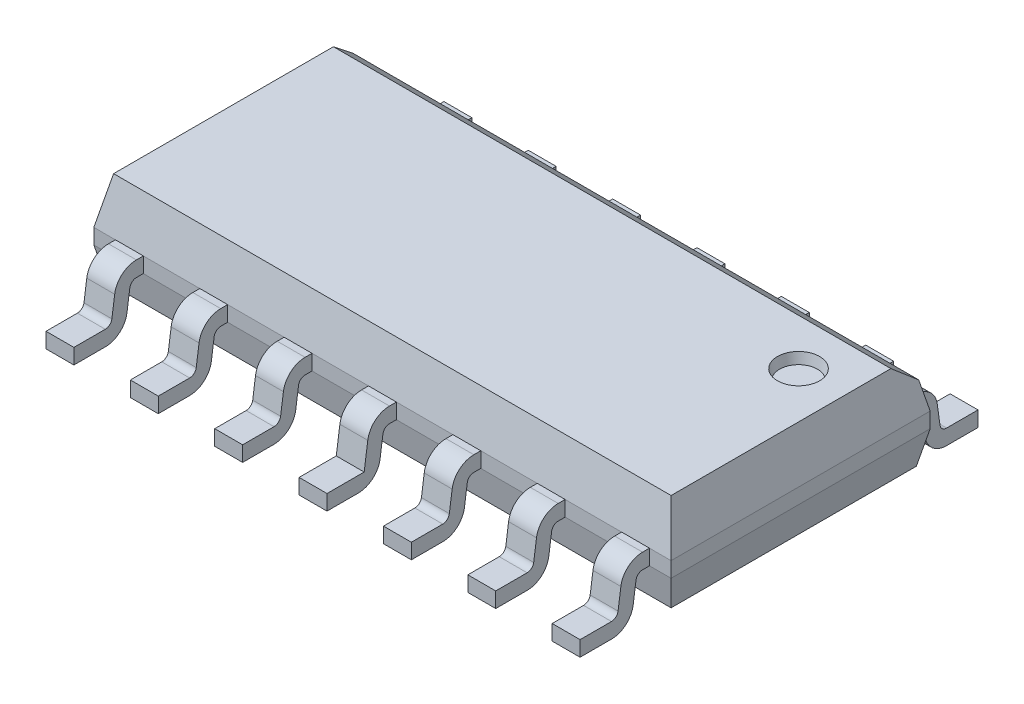
SolidWorks part; units mm, degrees
note: '?' marks a value the reader was unsure of.
ref_plane "Front Plane" through (0, 0, 0) normal (0, 0, 1) x (1, 0, 0)
ref_plane "Top Plane" through (0, 0, 0) normal (0, 1, 0) x (1, 0, 0)
ref_plane "Right Plane" through (0, 0, 0) normal (1, 0, 0) x (0, 0, -1)
ref_axis "Axis1" through (4.7795, 0, 0) along (-1, 0, 0)?
sketch "Sketch1" plane through (0, 0, 0) normal (0, 1, 0) x (1, 0, 0)
  line L1 (-4.345, 1.95) -> (4.345, 1.95)
  line L2 (-4.345, 1.95) -> (-4.345, -1.95)
  line L3 (-4.345, -1.95) -> (4.345, -1.95)
  line L4 (4.345, 1.95) -> (4.345, -1.95)
  dimension "D1" = 8.69
  dimension "D2" = 3.9
  dimension "D3" = 4.345
  dimension "D4" = 1.95
extrude "Extrude1" add sketch "Sketch1" along normal blind 0.7 draft 12 and the other way blind 0.23
sketch "Sketch2" plane through (0, -0.23, 0) normal (0, -1, 0) x (1, 0, 0)
  line L4 (-4.345, 1.95) -> (-4.345, -1.95)
  line L5 (-4.345, -1.95) -> (4.345, -1.95)
  line L6 (4.345, -1.95) -> (4.345, 1.95)
  line L7 (4.345, 1.95) -> (-4.345, 1.95)
  line L8 (-4.345, 1.95) -> (-4.345, -1.95)
  line L9 (-4.345, -1.95) -> (4.345, -1.95)
  line L10 (4.345, -1.95) -> (4.345, 1.95)
  line L11 (4.345, 1.95) -> (-4.345, 1.95)
  dimension "D1" = 0
extrude "Extrude2" add sketch "Sketch2" along normal blind 0.49 draft 12
chamfer "Chamfer1" distance 0.3 angle 38.5 1 edges at (0, 0.7, -1.8012)
sketch "Sketch3" plane through (0, 0.7, 0) normal (0, 1, 0) x (-1, 0, 0)
  circle A0 centre (-3.5015, -0.8119) radius 0.3175
extrude "Cut-Extrude1" cut sketch "Sketch3" against normal blind 0.15 draft 12
sketch "Sketch4" plane through (0, 0, 0) normal (1, 0, 0) x (0, 0, -1)
  line L0 (1.95, -0.23) -> (-1.95, -0.23) construction
  line L1 (1.95, 0) -> (-1.95, 0) construction
  line L2 (1.95, -0.23) -> (-1.95, -0.23)
  line L3 (1.95, 0) -> (-1.95, 0)
  line L4 (-1.8458, -0.72) -> (1.8458, -0.72) construction
  line L5 (2.995, -0.67) -> (2.4354, -0.67)
  line L6 (2.995, -0.67) -> (2.995, -0.9)
  line L7 (2.995, -0.9) -> (2.2355, -0.9)
  line L8 (2.155, -0.67) -> (2.155, -0.9) construction
  line L9 (-2.155, -0.67) -> (-2.4354, -0.67) construction
  line L10 (-2.155, -0.67) -> (-2.155, -0.9) construction
  line L11 (-2.155, -0.9) -> (-2.2355, -0.9) construction
  line L12 (-2.995, -0.67) -> (-2.995, -0.9)
  line L13 (1.95, 0) -> (2.3413, 0)
  line L14 (2.6703, 0) -> (2.6703, -0.23) construction
  line L15 (2.6703, -0.23) -> (2.1413, -0.23) construction
  line L16 (-1.95, 0) -> (-2.3413, 0)
  line L17 (-2.6934, 0) -> (-2.6934, -0.23) construction
  line L18 (-2.6934, -0.23) -> (-2.1413, -0.23) construction
  line L19 (2.3413, 0) -> (2.6703, 0) construction
  line L20 (2.4354, -0.67) -> (2.3413, 0)
  line L21 (2.2355, -0.9) -> (2.1413, -0.23)
  line L22 (2.1413, -0.23) -> (1.95, -0.23)
  line L23 (2.2355, -0.9) -> (2.155, -0.9) construction
  line L24 (2.4354, -0.67) -> (2.155, -0.67) construction
  line L25 (0, -1.1578) -> (0, -1.9582) construction
  line L26 (-2.2355, -0.9) -> (-2.1413, -0.23)
  line L27 (-2.4354, -0.67) -> (-2.3413, 0)
  line L28 (-2.1413, -0.23) -> (-1.95, -0.23)
  line L29 (-2.3413, 0) -> (-2.6934, 0) construction
  line L30 (-2.4354, -0.67) -> (-2.995, -0.67)
  line L31 (-2.2355, -0.9) -> (-2.995, -0.9)
  dimension "D1" = 0.84
  dimension "D2" = 5.99
  dimension "D3" = 2.995
  dimension "D4" = 0.18
  dimension "D5" = 0.23
  dimension "D6" = 0.23
extrude "Extrude3" add sketch "Sketch4" along normal blind 0.21 and the other way blind 0.21
pattern_linear "LPattern3" count 4 spacing 1.27 along (1, 0, 0) count 4 spacing 1.27 along (-1, 0, 0) of "Extrude3"
fillet "Fillet1" radius 0.1 27 edges at (-1.27, -0.23, 2.1413) (-1.27, -0.23, -2.1413) (-1.27, -0.67, -2.4354) (-1.27, -0.67, 2.4354) (-2.54, -0.23, 2.1413) (-2.54, -0.23, -2.1413) (-2.54, -0.67, -2.4354) (-2.54, -0.67, 2.4354) (-3.81, -0.23, 2.1413) (-3.81, -0.23, -2.1413) (-3.81, -0.67, -2.4354) (-3.81, -0.67, 2.4354) (1.27, -0.23, 2.1413) (1.27, -0.23, -2.1413) (1.27, -0.67, -2.4354) (1.27, -0.67, 2.4354) (2.54, -0.23, 2.1413) (2.54, -0.23, -2.1413) (2.54, -0.67, -2.4354) (2.54, -0.67, 2.4354) (3.81, -0.23, 2.1413) (3.81, -0.23, -2.1413) (3.81, -0.67, -2.4354) (3.81, -0.67, 2.4354) (0, -0.23, 2.1413) (0, -0.23, -2.1413) (0, -0.67, -2.4354)
fillet "Fillet2" radius 0.33 28 edges at (-1.27, 0, -2.3413) (-1.27, -0.9, -2.2355) (-1.27, 0, 2.3413) (-1.27, -0.9, 2.2355) (-2.54, 0, -2.3413) (-2.54, -0.9, -2.2355) (-2.54, 0, 2.3413) (-2.54, -0.9, 2.2355) (-3.81, 0, -2.3413) (-3.81, -0.9, -2.2355) (-3.81, 0, 2.3413) (-3.81, -0.9, 2.2355) (1.27, 0, -2.3413) (1.27, -0.9, -2.2355) (1.27, 0, 2.3413) (1.27, -0.9, 2.2355) (2.54, 0, -2.3413) (2.54, -0.9, -2.2355) (2.54, 0, 2.3413) (2.54, -0.9, 2.2355) (3.81, 0, -2.3413) (3.81, -0.9, -2.2355) (3.81, 0, 2.3413) (3.81, -0.9, 2.2355) (0, 0, -2.3413) (0, -0.9, -2.2355) (0, 0, 2.3413) (0, -0.9, 2.2355)
ref_plane "Board Surface" through (0, -0.9, 0) normal (0, 1, 0) x (-1, 0, 0)
sketch "Component_Outline" plane through (0, -0.9, 0) normal (0, 1, 0) x (-1, 0, 0)
  line L0 (4.345, -1.95) -> (4.02, -1.95)
  line L1 (4.02, -1.95) -> (4.02, -2.995)
  line L2 (4.02, -2.995) -> (3.6, -2.995)
  line L3 (3.6, -2.995) -> (3.6, -1.95)
  line L4 (3.6, -1.95) -> (2.75, -1.95)
  line L5 (2.75, -1.95) -> (2.75, -2.995)
  line L6 (2.75, -2.995) -> (2.33, -2.995)
  line L7 (2.33, -2.995) -> (2.33, -1.95)
  line L8 (2.33, -1.95) -> (1.48, -1.95)
  line L9 (1.48, -1.95) -> (1.48, -2.995)
  line L10 (1.48, -2.995) -> (1.06, -2.995)
  line L11 (1.06, -2.995) -> (1.06, -1.95)
  line L12 (1.06, -1.95) -> (0.21, -1.95)
  line L13 (0.21, -1.95) -> (0.21, -2.995)
  line L14 (0.21, -2.995) -> (-0.21, -2.995)
  line L15 (-0.21, -2.995) -> (-0.21, -1.95)
  line L16 (-0.21, -1.95) -> (-1.06, -1.95)
  line L17 (-1.06, -1.95) -> (-1.06, -2.995)
  line L18 (-1.06, -2.995) -> (-1.48, -2.995)
  line L19 (-1.48, -2.995) -> (-1.48, -1.95)
  line L20 (-1.48, -1.95) -> (-2.33, -1.95)
  line L21 (-2.33, -1.95) -> (-2.33, -2.995)
  line L22 (-2.33, -2.995) -> (-2.75, -2.995)
  line L23 (-2.75, -2.995) -> (-2.75, -1.95)
  line L24 (-2.75, -1.95) -> (-3.6, -1.95)
  line L25 (-3.6, -1.95) -> (-3.6, -2.995)
  line L26 (-3.6, -2.995) -> (-4.02, -2.995)
  line L27 (-4.02, -2.995) -> (-4.02, -1.95)
  line L28 (-4.02, -1.95) -> (-4.345, -1.95)
  line L29 (4.345, 0) -> (-4.345, 0) construction
  line L30 (4.345, -1.95) -> (4.345, 1.95) construction
  line L31 (-4.345, 1.95) -> (-4.345, -1.95) construction
  line L32 (-4.02, 1.95) -> (-4.345, 1.95)
  line L33 (-4.02, 2.995) -> (-4.02, 1.95)
  line L34 (-3.6, 2.995) -> (-4.02, 2.995)
  line L35 (-3.6, 1.95) -> (-3.6, 2.995)
  line L36 (-2.75, 1.95) -> (-3.6, 1.95)
  line L37 (-2.75, 2.995) -> (-2.75, 1.95)
  line L38 (-2.33, 2.995) -> (-2.75, 2.995)
  line L39 (-2.33, 1.95) -> (-2.33, 2.995)
  line L40 (-1.48, 1.95) -> (-2.33, 1.95)
  line L41 (-1.48, 2.995) -> (-1.48, 1.95)
  line L42 (-1.06, 2.995) -> (-1.48, 2.995)
  line L43 (-1.06, 1.95) -> (-1.06, 2.995)
  line L44 (-0.21, 1.95) -> (-1.06, 1.95)
  line L45 (-0.21, 2.995) -> (-0.21, 1.95)
  line L46 (0.21, 2.995) -> (-0.21, 2.995)
  line L47 (0.21, 1.95) -> (0.21, 2.995)
  line L48 (1.06, 1.95) -> (0.21, 1.95)
  line L49 (1.06, 2.995) -> (1.06, 1.95)
  line L50 (1.48, 2.995) -> (1.06, 2.995)
  line L51 (1.48, 1.95) -> (1.48, 2.995)
  line L52 (2.33, 1.95) -> (1.48, 1.95)
  line L53 (2.33, 2.995) -> (2.33, 1.95)
  line L54 (2.75, 2.995) -> (2.33, 2.995)
  line L55 (2.75, 1.95) -> (2.75, 2.995)
  line L56 (3.6, 1.95) -> (2.75, 1.95)
  line L57 (3.6, 2.995) -> (3.6, 1.95)
  line L58 (4.02, 2.995) -> (3.6, 2.995)
  line L59 (4.02, 1.95) -> (4.02, 2.995)
  line L60 (4.345, 1.95) -> (4.02, 1.95)
  line L61 (-4.345, -1.95) -> (-4.345, 1.95)
  line L62 (4.345, -1.95) -> (4.345, 1.95)
  line L63 (-3.81, -2.5224) -> (-3.81, -2.995) construction
  line L64 (-4.02, -2.5224) -> (-3.6, -2.5224) construction
  point P100 (-3.81, -2.7587)
